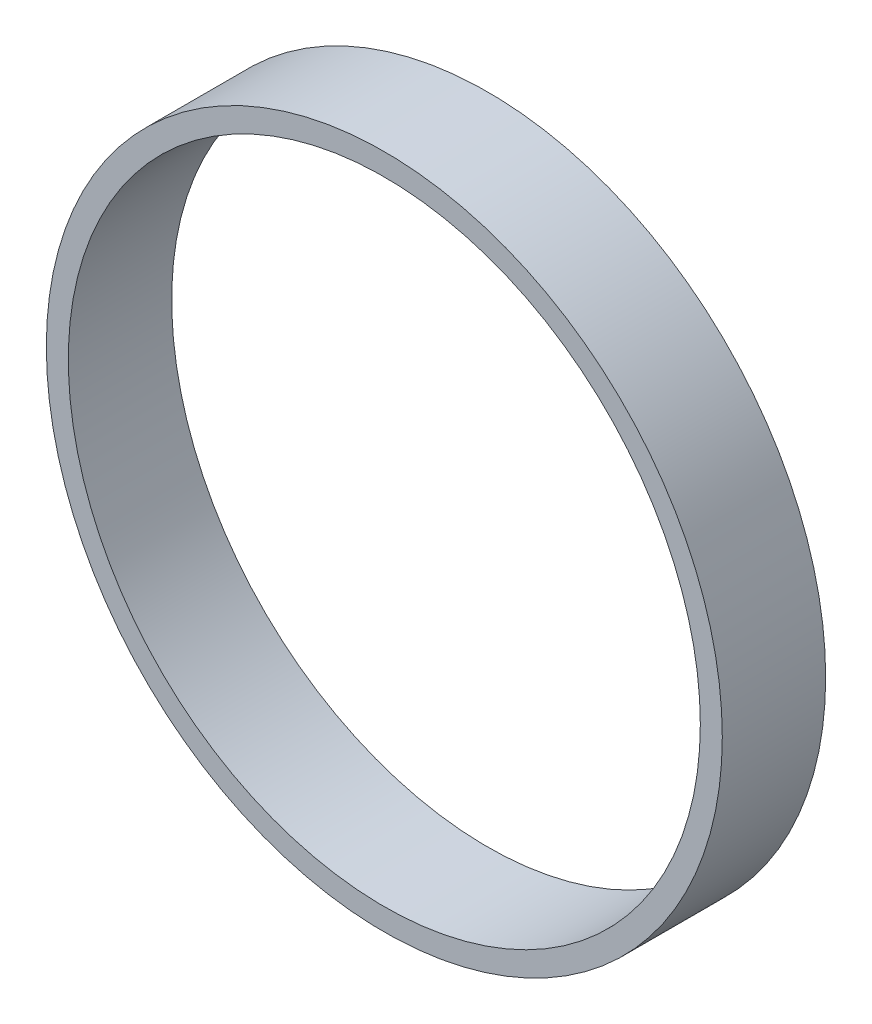
SolidWorks part; units mm, degrees
ref_plane "Front Plane" through (0, 0, 0) normal (0, 0, 1) x (1, 0, 0)
ref_plane "Top Plane" through (0, 0, 0) normal (0, 1, 0) x (1, 0, 0)
ref_plane "Right Plane" through (0, 0, 0) normal (1, 0, 0) x (0, 0, -1)
sketch "Sketch1" plane through (0, 0, 0) normal (0, 0, 1) x (1, 0, 0)
  circle A0 centre (0, 0) radius 77.65
  circle A1 centre (0, 0) radius 83.05
  dimension "Out_dia" = 166.1
  dimension "Thickness" = 5.4
extrude "BasePipe" add sketch "Sketch1" along normal mid plane 25.4
